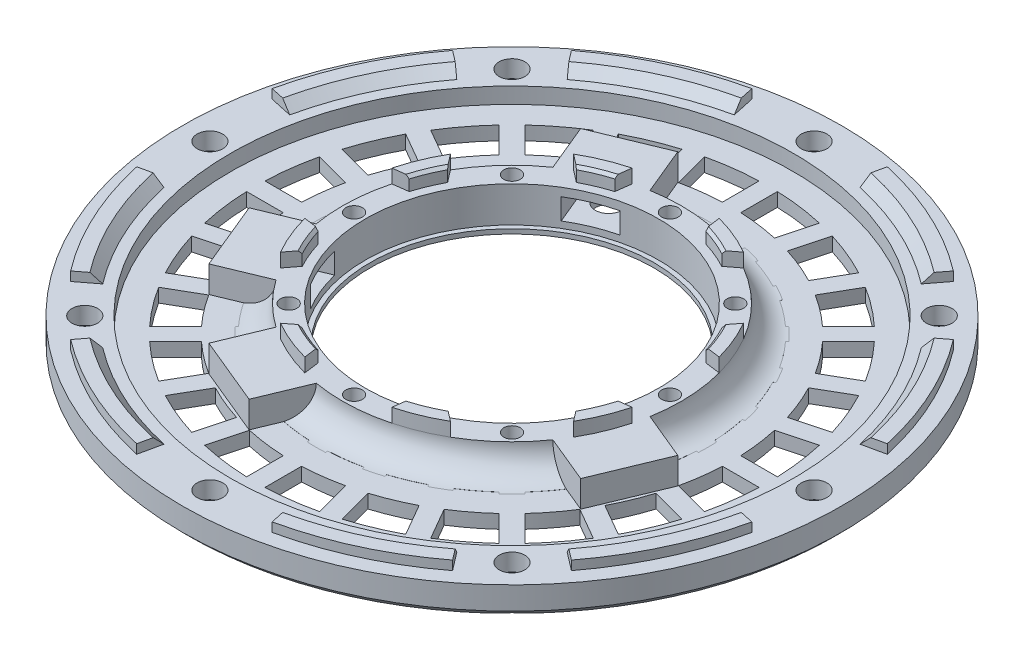
SolidWorks part; units mm, degrees
ref_plane "Front Plane" through (0, 0, 0) normal (0, 0, 1) x (1, 0, 0)
ref_plane "Top Plane" through (0, 0, 0) normal (0, 1, 0) x (1, 0, 0)
ref_plane "Right Plane" through (0, 0, 0) normal (1, 0, 0) x (0, 0, -1)
sketch "Sketch1" plane through (0, 0, 0) normal (0, 1, 0) x (1, 0, 0)
  circle A0 centre (0, 0) radius 16.025
  circle A1 centre (0, 0) radius 36
  dimension "D1" = 32.05
  dimension "D2" = 72
extrude "Boss-Extrude1" add sketch "Sketch1" along normal blind 1
sketch "Sketch2" plane through (0, 0, 0) normal (0, -1, 0) x (1, 0, 0)
  circle A0 centre (0, 0) radius 17.25 construction
  circle A1 centre (0, 0) radius 18.5 construction
  circle A2 centre (0, 0) radius 18.5
  circle A3 centre (0, 0) radius 16.025 construction
  circle A4 centre (0, 0) radius 16.025
  arc A5 (-1.2, 18.461) -> (-4.705, 17.8917) centre (0, 0) ccw construction
  point P3 (0, -17.25)
extrude "Boss-Extrude2" add sketch "Sketch2" against normal offset from surface (3.9 mm away) 3.9 up to face at (0, 0, 36)
fillet "Fillet1" radius 2.9 1 edges at (0, 1, 18.5)
sketch "Sketch4" plane through (0, 0, 0) normal (0, 1, 0) x (1, 0, 0)
  circle A0 centre (0, 0) radius 15.525
  circle A1 centre (0, 0) radius 36
  circle A2 centre (0, 0) radius 36
  circle A3 centre (0, 0) radius 16.025 construction
  dimension "D2" = 0.5
  dimension "D1" = 0
extrude "Boss-Extrude3" add sketch "Sketch4" against normal blind 0.5
sketch "Sketch5" plane through (0, 1, 0) normal (0, 1, 0) x (1, 0, 0)
  line L0 (27.99, -0.75) -> (19.9859, -0.75) construction
  line L1 (19.9859, 0.75) -> (27.99, 0.75) construction
  line L2 (27.99, -0.75) -> (19.9859, -0.75) construction
  line L3 (19.9859, 0.75) -> (27.99, 0.75) construction
  line L4 (0, 0) -> (36, 0) construction
  line L5 (0, 0) -> (34.7733, 9.3175) construction
  line L6 (34.7733, 9.3175) -> (36, 0) construction
  line L7 (0, 0) -> (35.3867, 4.6587) construction
  line L8 (27.99, 1) -> (21.1263, 1)
  line L9 (27.295, 6.2784) -> (20.6653, 4.502)
  line L10 (27.99, -1) -> (21.1263, -1)
  line L11 (27.295, -6.2784) -> (20.6653, -4.502)
  line L12 (26.7774, -8.2103) -> (20.1477, -6.4338)
  line L13 (24.74, -13.129) -> (18.796, -9.6971)
  line L14 (23.74, -14.861) -> (17.796, -11.4292)
  line L15 (20.499, -19.0848) -> (15.6457, -14.2315)
  line L16 (19.0848, -20.499) -> (14.2315, -15.6457)
  line L17 (14.861, -23.74) -> (11.4292, -17.796)
  line L18 (13.129, -24.74) -> (9.6971, -18.796)
  line L19 (8.2103, -26.7774) -> (6.4338, -20.1477)
  line L20 (6.2784, -27.295) -> (4.502, -20.6653)
  line L21 (1, -27.99) -> (1, -21.1263)
  line L22 (-1, -27.99) -> (-1, -21.1263)
  line L23 (-6.2784, -27.295) -> (-4.502, -20.6653)
  line L24 (-8.2103, -26.7774) -> (-6.4338, -20.1477)
  line L25 (-13.129, -24.74) -> (-9.6971, -18.796)
  line L26 (-14.861, -23.74) -> (-11.4292, -17.796)
  line L27 (-19.0848, -20.499) -> (-14.2315, -15.6457)
  line L28 (-20.499, -19.0848) -> (-15.6457, -14.2315)
  line L29 (-23.74, -14.861) -> (-17.796, -11.4292)
  line L30 (-24.74, -13.129) -> (-18.796, -9.6971)
  line L31 (-26.7774, -8.2103) -> (-20.1477, -6.4338)
  line L32 (-27.295, -6.2784) -> (-20.6653, -4.502)
  line L33 (-27.99, -1) -> (-21.1263, -1)
  line L34 (-27.99, 1) -> (-21.1263, 1)
  line L35 (-27.295, 6.2784) -> (-20.6653, 4.502)
  line L36 (-26.7774, 8.2103) -> (-20.1477, 6.4338)
  line L37 (-24.74, 13.129) -> (-18.796, 9.6971)
  line L38 (-23.74, 14.861) -> (-17.796, 11.4292)
  line L39 (-20.499, 19.0848) -> (-15.6457, 14.2315)
  line L40 (-19.0848, 20.499) -> (-14.2315, 15.6457)
  line L41 (-14.861, 23.74) -> (-11.4292, 17.796)
  line L42 (-13.129, 24.74) -> (-9.6971, 18.796)
  line L43 (-8.2103, 26.7774) -> (-6.4338, 20.1477)
  line L44 (-6.2784, 27.295) -> (-4.502, 20.6653)
  line L45 (-1, 27.99) -> (-1, 21.1263)
  line L46 (1, 27.99) -> (1, 21.1263)
  line L47 (6.2784, 27.295) -> (4.502, 20.6653)
  line L48 (8.2103, 26.7774) -> (6.4338, 20.1477)
  line L49 (13.129, 24.74) -> (9.6971, 18.796)
  line L50 (14.861, 23.74) -> (11.4292, 17.796)
  line L51 (19.0848, 20.499) -> (14.2315, 15.6457)
  line L52 (20.499, 19.0848) -> (15.6457, 14.2315)
  line L53 (23.74, 14.861) -> (17.796, 11.4292)
  line L54 (24.74, 13.129) -> (18.796, 9.6971)
  line L55 (26.7774, 8.2103) -> (20.1477, 6.4338)
  line L56 (0, 0) -> (21.1263, 1) construction
  circle A0 centre (0, 0) radius 21.15 construction
  circle A2 centre (0, 0) radius 36 construction
  arc A3 (21.1263, 1) -> (20.6653, 4.502) centre (0, 0) ccw
  arc A4 (27.99, 1) -> (27.295, 6.2784) centre (0, 0) ccw
  arc A5 (27.295, -6.2784) -> (27.99, -1) centre (0, 0) ccw
  arc A6 (20.6653, -4.502) -> (21.1263, -1) centre (0, 0) ccw
  arc A7 (24.74, -13.129) -> (26.7774, -8.2103) centre (0, 0) ccw
  arc A8 (18.796, -9.6971) -> (20.1477, -6.4338) centre (0, 0) ccw
  arc A9 (20.499, -19.0848) -> (23.74, -14.861) centre (0, 0) ccw
  arc A10 (15.6457, -14.2315) -> (17.796, -11.4292) centre (0, 0) ccw
  arc A11 (14.861, -23.74) -> (19.0848, -20.499) centre (0, 0) ccw
  arc A12 (11.4292, -17.796) -> (14.2315, -15.6457) centre (0, 0) ccw
  arc A13 (8.2103, -26.7774) -> (13.129, -24.74) centre (0, 0) ccw
  arc A14 (6.4338, -20.1477) -> (9.6971, -18.796) centre (0, 0) ccw
  arc A15 (1, -27.99) -> (6.2784, -27.295) centre (0, 0) ccw
  arc A16 (1, -21.1263) -> (4.502, -20.6653) centre (0, 0) ccw
  arc A17 (-6.2784, -27.295) -> (-1, -27.99) centre (0, 0) ccw
  arc A18 (-4.502, -20.6653) -> (-1, -21.1263) centre (0, 0) ccw
  arc A19 (-13.129, -24.74) -> (-8.2103, -26.7774) centre (0, 0) ccw
  arc A20 (-9.6971, -18.796) -> (-6.4338, -20.1477) centre (0, 0) ccw
  arc A21 (-19.0848, -20.499) -> (-14.861, -23.74) centre (0, 0) ccw
  arc A22 (-14.2315, -15.6457) -> (-11.4292, -17.796) centre (0, 0) ccw
  arc A23 (-23.74, -14.861) -> (-20.499, -19.0848) centre (0, 0) ccw
  arc A24 (-17.796, -11.4292) -> (-15.6457, -14.2315) centre (0, 0) ccw
  arc A25 (-26.7774, -8.2103) -> (-24.74, -13.129) centre (0, 0) ccw
  arc A26 (-20.1477, -6.4338) -> (-18.796, -9.6971) centre (0, 0) ccw
  arc A27 (-27.99, -1) -> (-27.295, -6.2784) centre (0, 0) ccw
  arc A28 (-21.1263, -1) -> (-20.6653, -4.502) centre (0, 0) ccw
  arc A29 (-27.295, 6.2784) -> (-27.99, 1) centre (0, 0) ccw
  arc A30 (-20.6653, 4.502) -> (-21.1263, 1) centre (0, 0) ccw
  arc A31 (-24.74, 13.129) -> (-26.7774, 8.2103) centre (0, 0) ccw
  arc A32 (-18.796, 9.6971) -> (-20.1477, 6.4338) centre (0, 0) ccw
  arc A33 (-20.499, 19.0848) -> (-23.74, 14.861) centre (0, 0) ccw
  arc A34 (-15.6457, 14.2315) -> (-17.796, 11.4292) centre (0, 0) ccw
  arc A35 (-14.861, 23.74) -> (-19.0848, 20.499) centre (0, 0) ccw
  arc A36 (-11.4292, 17.796) -> (-14.2315, 15.6457) centre (0, 0) ccw
  arc A37 (-8.2103, 26.7774) -> (-13.129, 24.74) centre (0, 0) ccw
  arc A38 (-6.4338, 20.1477) -> (-9.6971, 18.796) centre (0, 0) ccw
  arc A39 (-1, 27.99) -> (-6.2784, 27.295) centre (0, 0) ccw
  arc A40 (-1, 21.1263) -> (-4.502, 20.6653) centre (0, 0) ccw
  arc A41 (6.2784, 27.295) -> (1, 27.99) centre (0, 0) ccw
  arc A42 (4.502, 20.6653) -> (1, 21.1263) centre (0, 0) ccw
  arc A43 (13.129, 24.74) -> (8.2103, 26.7774) centre (0, 0) ccw
  arc A44 (9.6971, 18.796) -> (6.4338, 20.1477) centre (0, 0) ccw
  arc A45 (19.0848, 20.499) -> (14.861, 23.74) centre (0, 0) ccw
  arc A46 (14.2315, 15.6457) -> (11.4292, 17.796) centre (0, 0) ccw
  arc A47 (23.74, 14.861) -> (20.499, 19.0848) centre (0, 0) ccw
  arc A48 (17.796, 11.4292) -> (15.6457, 14.2315) centre (0, 0) ccw
  arc A49 (26.7774, 8.2103) -> (24.74, 13.129) centre (0, 0) ccw
  arc A50 (20.1477, 6.4338) -> (18.796, 9.6971) centre (0, 0) ccw
  dimension "D1" = 15
  dimension "D2" = 1
  dimension "D4" = 21.15
  dimension "D3" = 24
extrude "Cut-Extrude1" cut sketch "Sketch5" against normal through all both and the other way through all
sketch "Sketch22" plane through (0, -0.5, 0) normal (0, -1, 0) x (1, 0, 0)
  circle A0 centre (0, 0) radius 21.15
  circle A1 centre (0, 0) radius 24.0078
  arc A2 (-14.861, 23.74) -> (-19.0848, 20.499) centre (0, 0) ccw construction
  dimension "D1" = 4
extrude "Boss-Extrude10" add sketch "Sketch22" against normal up to surface (1.5 mm away) up to face at (0, 1, 0)
sketch "Sketch7" plane through (0, 3.9, 0) normal (0, 1, 0) x (1, 0, 0)
  line L0 (0, 0) -> (0, 17.25) construction
  circle A0 centre (0, 17.25) radius 0.9
  circle A1 centre (12.1976, 12.1976) radius 0.9
  circle A2 centre (17.25, 0) radius 0.9
  circle A3 centre (12.1976, -12.1976) radius 0.9
  circle A4 centre (0, -17.25) radius 0.9
  circle A5 centre (-12.1976, -12.1976) radius 0.9
  circle A6 centre (-17.25, 0) radius 0.9
  circle A7 centre (-12.1976, 12.1976) radius 0.9
  point P21 (0, 0)
  dimension "D1" = 1.8
  dimension "D2" = 8
extrude "Cut-Extrude2" cut sketch "Sketch7" against normal through all
sketch "Sketch8" plane through (0, 1, 0) normal (0, 1, 0) x (1, 0, 0)
  arc A0 (-30.7407, -0.7544) -> (-30.0499, -6.5245) centre (0, 0) ccw construction
  arc A1 (-30.7407, -0.7544) -> (-30.0499, -6.5245) centre (0, 0) ccw construction
  arc A2 (-30.0499, 6.5245) -> (-30.7407, 0.7544) centre (0, 0) ccw construction
  arc A3 (-30.0499, 6.5245) -> (-30.7407, 0.7544) centre (0, 0) ccw construction
  circle A5 centre (0, 0) radius 30.75
  circle A6 centre (0, 0) radius 36 construction
  circle A7 centre (0, 0) radius 36
extrude "Boss-Extrude4" add sketch "Sketch8" along normal blind 1.7378
sketch "Sketch9" plane through (0, 2.7378, 0) normal (0, 1, 0) x (1, 0, 0)
  line L0 (0, 0) -> (-30.0499, 6.5245) construction
  line L1 (0, 0) -> (-30.0499, -6.5245) construction
  line L2 (-30.0499, 6.5245) -> (-30.0499, -6.5245) construction
  line L3 (-27.3707, 21.0023) -> (-23.9989, 18.415) construction
  line L4 (0, 0) -> (0, 36) construction
  line L5 (0, 0) -> (-25.4558, 25.4558) construction
  line L6 (-24.3956, 18.7194) -> (0, 0) construction
  line L7 (-24.3956, 18.7194) -> (-28.5607, 21.9154) construction
  line L8 (-30.0499, 6.5245) -> (-35.1803, 7.6384) construction
  line L9 (-27.3521, 20.862) -> (-25.3687, 19.3401)
  line L10 (-31.2086, 14.47) -> (0, 0) construction
  line L11 (-33.5954, 7.3966) -> (-31.1523, 6.8662)
  line L12 (-7.3966, 33.5954) -> (-6.8662, 31.1523)
  line L13 (-20.862, 27.3521) -> (-19.3401, 25.3687)
  arc A0 (-30.0499, 6.5245) -> (-24.3956, 18.7194) centre (0, 0) cw construction
  arc A1 (-35.1803, 7.6384) -> (-28.5607, 21.9154) centre (0, 0) cw construction
  circle A2 centre (0, 0) radius 36 construction
  circle A3 centre (0, 0) radius 30.75 construction
  arc A4 (-27.2914, 20.9414) -> (-33.6168, 7.2989) centre (0, 0) ccw construction
  arc A5 (-31.1523, 6.8662) -> (-25.3687, 19.3401) centre (0, 0) cw
  arc A6 (-33.5954, 7.3966) -> (-27.3521, 20.862) centre (0, 0) cw
  circle A7 centre (0, 0) radius 36 construction
  arc A8 (-6.8662, 31.1523) -> (-19.3401, 25.3687) centre (0, 0) ccw
  arc A9 (-7.3966, 33.5954) -> (-20.862, 27.3521) centre (0, 0) ccw
  dimension "D2" = 0.1
  dimension "D3" = 45
  dimension "D4" = 0.1
  dimension "D1" = 2.5
extrude "Boss-Extrude5" add sketch "Sketch9" along normal blind 1
ref_axis "Axis1" through (0, -0.795, 0) along (0, 1, 0)
pattern_circular "CirPattern1" count 4 over 360 about axis through (0, -0.795, 0) along (0, 1, 0) of "Boss-Extrude5"
chamfer "Chamfer1" distance 1 angle 45 8 edges at (-28.9406, 3.7378, -13.4184) (-13.4184, 3.7378, -28.9406) (13.4184, 3.7378, -28.9406) (28.9406, 3.7378, -13.4184) (28.9406, 3.7378, 13.4184) (13.4184, 3.7378, 28.9406) (-13.4184, 3.7378, 28.9406) (-28.9406, 3.7378, 13.4184)
sketch "Sketch10" plane through (0, 2.7378, 0) normal (0, 1, 0) x (1, 0, 0)
  line L0 (0, 0) -> (0, 36) construction
  circle A0 centre (0, 0) radius 36 construction
  circle A1 centre (0, 33) radius 1.4 construction
  circle A2 centre (0, 33) radius 1.4
  circle A3 centre (23.3345, 23.3345) radius 1.4
  circle A4 centre (33, 0) radius 1.4
  circle A5 centre (23.3345, -23.3345) radius 1.4
  circle A6 centre (0, -33) radius 1.4
  circle A7 centre (-23.3345, -23.3345) radius 1.4
  circle A8 centre (-33, 0) radius 1.4
  circle A9 centre (-23.3345, 23.3345) radius 1.4
  point P26 (0, 0)
  dimension "D1" = 8
extrude "Cut-Extrude3" cut sketch "Sketch10" against normal through all both and the other way through all
chamfer "Chamfer2" distance 0.75 angle 45 1 edges at (0, -0.5, 36)
hole_wizard "CSK for M2.5 Flat Head Machine Screw1" positions "Sketch11" profile "Sketch12" countersink size "M2.5" standard "ANSI Metric" end condition through all
sketch "Sketch11" plane through (0, -0.5, 0) normal (0, -1, 0) x (-1, 0, 0)
  point P0 (0, -33)
  point P3 (23.3345, -23.3345)
  point P6 (33, 0)
  point P9 (23.3345, 23.3345)
  point P12 (0, 33)
  point P15 (-23.3345, 23.3345)
  point P18 (-33, 0)
  point P21 (-23.3345, -23.3345)
sketch "Sketch12" plane through (0, -0.5, 33) normal (1, 0, 0) x (0, 0, -1)
  line L0 (0, 0) -> (0, 4.4)
  line L1 (0, 4.4) -> (1.35, 4.4)
  line L2 (1.35, 4.4) -> (1.35, 1.4)
  line L3 (1.35, 1.4) -> (2.75, 0)
  line L5 (2.75, 0) -> (0, 0)
  line L6 (-1.35, 1.4) -> (-2.75, 0) construction
  line L11 (0, -6.35) -> (0, 107.95) construction
  dimension "Thru Hole Dia." = 2.7
  dimension "Thru Hole Depth" = 4.4
  dimension "Near C'Sink Dia." = 5.5
  dimension "Near C'Sink Angle" = 90
sketch "Sketch13" plane through (0, 3.9, 0) normal (0, 1, 0) x (1, 0, 0)
  line L0 (0, 0) -> (-7.0796, 17.0918) construction
  line L1 (0, 0) -> (0, 18.5) construction
  line L2 (-9.2808, 16.0037) -> (-7.9403, 14.9751)
  line L3 (-4.7538, 17.8788) -> (-4.9743, 16.2037)
  line L4 (4.7538, 17.8788) -> (4.9743, 16.2037)
  line L5 (9.2808, 16.0037) -> (7.9403, 14.9751)
  line L6 (16.0037, 9.2808) -> (14.9751, 7.9403)
  line L7 (17.8788, 4.7538) -> (16.2037, 4.9743)
  line L8 (17.8788, -4.7538) -> (16.2037, -4.9743)
  line L9 (16.0037, -9.2808) -> (14.9751, -7.9403)
  line L10 (9.2808, -16.0037) -> (7.9403, -14.9751)
  line L11 (4.7538, -17.8788) -> (4.9743, -16.2037)
  line L12 (-4.7538, -17.8788) -> (-4.9743, -16.2037)
  line L13 (-9.2808, -16.0037) -> (-7.9403, -14.9751)
  line L14 (-16.0037, -9.2808) -> (-14.9751, -7.9403)
  line L15 (-17.8788, -4.7538) -> (-16.2037, -4.9743)
  line L16 (-17.8788, 4.7538) -> (-16.2037, 4.9743)
  line L17 (-16.0037, 9.2808) -> (-14.9751, 7.9403)
  circle A0 centre (0, 0) radius 18.5 construction
  arc A1 (-7.9403, 14.9751) -> (-4.9743, 16.2037) centre (0, 0) cw
  arc A2 (-9.2808, 16.0037) -> (-4.7538, 17.8788) centre (0, 0) cw
  arc A3 (4.9743, 16.2037) -> (7.9403, 14.9751) centre (0, 0) cw
  arc A4 (4.7538, 17.8788) -> (9.2808, 16.0037) centre (0, 0) cw
  arc A5 (14.9751, 7.9403) -> (16.2037, 4.9743) centre (0, 0) cw
  arc A6 (16.0037, 9.2808) -> (17.8788, 4.7538) centre (0, 0) cw
  arc A7 (16.2037, -4.9743) -> (14.9751, -7.9403) centre (0, 0) cw
  arc A8 (17.8788, -4.7538) -> (16.0037, -9.2808) centre (0, 0) cw
  arc A9 (7.9403, -14.9751) -> (4.9743, -16.2037) centre (0, 0) cw
  arc A10 (9.2808, -16.0037) -> (4.7538, -17.8788) centre (0, 0) cw
  arc A11 (-4.9743, -16.2037) -> (-7.9403, -14.9751) centre (0, 0) cw
  arc A12 (-4.7538, -17.8788) -> (-9.2808, -16.0037) centre (0, 0) cw
  arc A13 (-14.9751, -7.9403) -> (-16.2037, -4.9743) centre (0, 0) cw
  arc A14 (-16.0037, -9.2808) -> (-17.8788, -4.7538) centre (0, 0) cw
  arc A15 (-16.2037, 4.9743) -> (-14.9751, 7.9403) centre (0, 0) cw
  arc A16 (-17.8788, 4.7538) -> (-16.0037, 9.2808) centre (0, 0) cw
  point P12 (-6.4865, 15.6598)
  point P20 (6.4865, 15.6598)
  point P25 (15.6598, 6.4865)
  point P30 (15.6598, -6.4865)
  point P35 (6.4865, -15.6598)
  point P40 (-6.4865, -15.6598)
  point P45 (-15.6598, -6.4865)
  point P50 (-15.6598, 6.4865)
  point P51 (0, 0)
  dimension "D1" = 22.5
  dimension "D2" = 30
  dimension "D3" = 1.55
  dimension "D4" = 4.9
  dimension "D5" = 8
extrude "Boss-Extrude6" add sketch "Sketch13" along normal blind 1.5
chamfer "Chamfer3" distance 0.3 angle 45 8 edges at (-15.6598, 5.4, -6.4865) (-15.6598, 5.4, 6.4865) (-6.4865, 5.4, 15.6598) (6.4865, 5.4, 15.6598) (15.6598, 5.4, 6.4865) (15.6598, 5.4, -6.4865) (6.4865, 5.4, -15.6598) (-6.4865, 5.4, -15.6598)
sketch "Sketch14" plane through (0, -0.5, 0) normal (0, -1, 0) x (1, 0, 0)
  line L0 (0, 0) -> (25.4558, -25.4558) construction
  line L1 (0, 0) -> (0, -36) construction
  line L6 (0, 0) -> (-19.9789, 8.2755) construction
  line L7 (0, 0) -> (-8.2755, -19.9789) construction
  circle A0 centre (0, 0) radius 36 construction
  circle A1 centre (0, 0) radius 16.025 construction
  circle A6 centre (-18.0157, 7.4623) radius 1.45
  circle A7 centre (-18.0157, 7.4623) radius 2.125 construction
  circle A9 centre (-7.4623, -18.0157) radius 1.45
  circle A10 centre (-7.4623, -18.0157) radius 2.125 construction
  circle A11 centre (18.0157, 7.4623) radius 1.45
  circle A12 centre (-7.4623, 18.0157) radius 1.45
  point P25 (-14.8052, 6.1325)
  point P28 (-16.676, 6.9074)
  dimension "D2" = 2.9
  dimension "D3" = 3.475
  dimension "D5" = 4.25
  dimension "D7" = 21.625
  dimension "D1" = 45
  dimension "D4" = 112.5
  dimension "D6" = 22.5
sketch "Sketch15" plane through (0, 1, 0) normal (0, 1, 0) x (1, 0, 0)
  line L0 (-9.8825, 13.2519) -> (-12.8051, 20.3077)
  line L1 (-9.8825, 13.2519) -> (-2.3825, 16.3585)
  line L2 (-12.8051, 20.3077) -> (-5.3051, 23.4143)
  line L3 (-2.3825, 16.3585) -> (-5.3051, 23.4143)
  line L4 (-9.8825, 13.2519) -> (-5.3051, 23.4143) construction
  line L5 (-12.8051, 20.3077) -> (-2.3825, 16.3585) construction
  line L6 (0, 0) -> (-8.2755, 19.9789) construction
  line L7 (2.3825, 16.3585) -> (5.3051, 23.4143) [skipped]
  line L8 (2.3825, 16.3585) -> (9.8825, 13.2519) [skipped]
  line L9 (5.3051, 23.4143) -> (12.8051, 20.3077) [skipped]
  line L10 (9.8825, 13.2519) -> (12.8051, 20.3077) [skipped]
  line L11 (2.3825, 16.3585) -> (12.8051, 20.3077) construction
  line L12 (5.3051, 23.4143) -> (9.8825, 13.2519) construction
  line L13 (13.2519, 9.8825) -> (20.3077, 12.8051) [skipped]
  line L14 (13.2519, 9.8825) -> (16.3585, 2.3825) [skipped]
  line L15 (20.3077, 12.8051) -> (23.4143, 5.3051) [skipped]
  line L16 (16.3585, 2.3825) -> (23.4143, 5.3051) [skipped]
  line L17 (13.2519, 9.8825) -> (23.4143, 5.3051) construction
  line L18 (20.3077, 12.8051) -> (16.3585, 2.3825) construction
  line L19 (16.3585, -2.3825) -> (23.4143, -5.3051)
  line L20 (16.3585, -2.3825) -> (13.2519, -9.8825)
  line L21 (23.4143, -5.3051) -> (20.3077, -12.8051)
  line L22 (13.2519, -9.8825) -> (20.3077, -12.8051)
  line L23 (16.3585, -2.3825) -> (20.3077, -12.8051) construction
  line L24 (23.4143, -5.3051) -> (13.2519, -9.8825) construction
  line L25 (9.8825, -13.2519) -> (12.8051, -20.3077) [skipped]
  line L26 (9.8825, -13.2519) -> (2.3825, -16.3585) [skipped]
  line L27 (12.8051, -20.3077) -> (5.3051, -23.4143) [skipped]
  line L28 (2.3825, -16.3585) -> (5.3051, -23.4143) [skipped]
  line L29 (9.8825, -13.2519) -> (5.3051, -23.4143) construction
  line L30 (12.8051, -20.3077) -> (2.3825, -16.3585) construction
  line L31 (-2.3825, -16.3585) -> (-5.3051, -23.4143)
  line L32 (-2.3825, -16.3585) -> (-9.8825, -13.2519)
  line L33 (-5.3051, -23.4143) -> (-12.8051, -20.3077)
  line L34 (-9.8825, -13.2519) -> (-12.8051, -20.3077)
  line L35 (-2.3825, -16.3585) -> (-12.8051, -20.3077) construction
  line L36 (-5.3051, -23.4143) -> (-9.8825, -13.2519) construction
  line L37 (-13.2519, -9.8825) -> (-20.3077, -12.8051)
  line L38 (-13.2519, -9.8825) -> (-16.3585, -2.3825)
  line L39 (-20.3077, -12.8051) -> (-23.4143, -5.3051)
  line L40 (-16.3585, -2.3825) -> (-23.4143, -5.3051)
  line L41 (-13.2519, -9.8825) -> (-23.4143, -5.3051) construction
  line L42 (-20.3077, -12.8051) -> (-16.3585, -2.3825) construction
  line L43 (-16.3585, 2.3825) -> (-23.4143, 5.3051) [skipped]
  line L44 (-16.3585, 2.3825) -> (-13.2519, 9.8825) [skipped]
  line L45 (-23.4143, 5.3051) -> (-20.3077, 12.8051) [skipped]
  line L46 (-13.2519, 9.8825) -> (-20.3077, 12.8051) [skipped]
  line L47 (-16.3585, 2.3825) -> (-20.3077, 12.8051) construction
  line L48 (-23.4143, 5.3051) -> (-13.2519, 9.8825) construction
  line L49 (0, 0) -> (-10.7181, 25.8758) construction
  arc A0 (-12.8595, 20.2733) -> (-16.2542, 17.6685) centre (0, 0) ccw construction
  arc A1 (-8.2103, 26.7774) -> (-13.129, 24.74) centre (0, 0) ccw construction
  circle A2 centre (0, 0) radius 16.025 construction
  point P1 (-7.5938, 18.3331)
  point P9 (7.5938, 18.3331)
  point P18 (18.3331, 7.5938)
  point P23 (18.3331, -7.5938)
  point P28 (7.5938, -18.3331)
  point P33 (-7.5938, -18.3331)
  point P38 (-18.3331, -7.5938)
  point P43 (-18.3331, 7.5938)
  point P48 (0, 0)
  dimension "D1" = 7.5
  dimension "D2" = 8
extrude "Boss-Extrude7" add sketch "Sketch15" along normal up to surface (2.9 mm away) up to face at (0, 3.9, -16.35)
extrude "Cut-Extrude4" cut sketch "Sketch14" against normal blind 3.5
sketch "Sketch16" [suppressed] plane through (0, -0.5, 0) normal (0, -1, 0) x (1, 0, 0)
  line L0 (0, 0) -> (23.3345, -23.3345) construction
  line L1 (9.9327, 7.9941) -> (22.7049, -7.8756) construction
  line L2 (0, 0) -> (0, -17.25) construction
  line L3 (0, 0) -> (9.9327, 7.9941) construction
  line L4 (19.041, 8.4876) -> (13.7643, 13.7643) construction
  line L5 (0, 0) -> (13.7643, 13.7643) construction
  line L6 (25.4316, -5.6811) -> (27.9064, -3.2063) construction
  line L7 (27.9064, -3.2063) -> (12.3501, 12.3501) construction
  circle A0 centre (0, 0) radius 12.75 construction
  circle A1 centre (25.4316, -5.6811) radius 1.65
  circle A2 centre (25.4316, -5.6811) radius 3.5 construction
  circle A3 centre (18.0157, 7.4623) radius 1.45 construction
  circle A4 centre (5.6811, -25.4316) radius 1.65
  dimension "D1" = 25.5
  dimension "D2" = 3.3
  dimension "D3" = 7
  dimension "D4" = 2
  dimension "D5" = 22
sketch "Sketch17" [suppressed] plane through (0, -0.5, 0) normal (0, -1, 0) x (1, 0, 0)
  line L0 (24.74, -13.129) -> (18.796, -9.6971) construction
  line L1 (24.74, -13.129) -> (18.796, -9.6971)
  line L2 (0, 0) -> (12.1976, -12.1976) construction
  line L3 (13.129, -24.74) -> (9.6971, -18.796)
  arc A0 (18.796, -9.6971) -> (20.1477, -6.4338) centre (0, 0) ccw construction
  arc A1 (24.74, -13.129) -> (26.7774, -8.2103) centre (0, 0) ccw construction
  arc A4 (18.796, -9.6971) -> (19.6572, -7.8049) centre (0, 0) ccw
  arc A5 (24.74, -13.129) -> (25.4284, -11.7403) centre (0, 0) ccw
  arc A8 (25.4284, -11.7403) -> (19.6572, -7.8049) centre (25.1212, -5.9915) ccw
  arc A9 (11.7403, -25.4284) -> (7.8049, -19.6572) centre (5.9915, -25.1212) cw
  arc A10 (13.129, -24.74) -> (11.7403, -25.4284) centre (0, 0) cw
  arc A11 (9.6971, -18.796) -> (7.8049, -19.6572) centre (0, 0) cw
extrude "Boss-Extrude8" [suppressed] add sketch "Sketch17" against normal up to surface (1.5 mm away)
sketch "Sketch18" [suppressed] plane through (0, 1, 0) normal (0, 1, 0) x (1, 0, 0)
  line L0 (0, 0) -> (25.4316, 5.6811) construction
  line L1 (24.5595, 9.5849) -> (28.8833, 10.5508)
  line L2 (26.3036, 1.7774) -> (30.6274, 2.7432)
  line L3 (0, 0) -> (23.3345, 23.3345) construction
  line L4 (9.5849, 24.5595) -> (10.5508, 28.8833)
  line L5 (1.7774, 26.3036) -> (2.7432, 30.6274)
  arc A0 (24.5595, 9.5849) -> (26.3036, 1.7774) centre (25.4316, 5.6811) ccw
  circle A1 centre (0, 0) radius 30.75 construction
  circle A2 centre (0, 0) radius 30.75 construction
  arc A3 (30.6274, 2.7432) -> (28.8833, 10.5508) centre (0, 0) ccw
  arc A4 (2.7432, 30.6274) -> (10.5508, 28.8833) centre (0, 0) cw
  arc A5 (9.5849, 24.5595) -> (1.7774, 26.3036) centre (5.6811, 25.4316) cw
  circle A6 centre (23.3345, 23.3345) radius 1.4 construction
  dimension "D1" = 8
extrude "Boss-Extrude9" [suppressed] add sketch "Sketch18" along normal up to surface (1.7378 mm away)
extrude "Cut-Extrude5" [suppressed] cut sketch "Sketch16" against normal through all
sketch "Sketch19" [suppressed] plane through (0, 2.7378, 0) normal (0, 1, 0) x (1, 0, 0)
  line L0 (0, 0) -> (25.1212, 5.9915) construction
  line L1 (28.1539, 6.7147) -> (26.0112, 8.9794)
  line L2 (26.0112, 8.9794) -> (22.9785, 8.2561)
  line L3 (22.9785, 8.2561) -> (22.0886, 5.2682)
  line L4 (22.0886, 5.2682) -> (24.2313, 3.0035)
  line L5 (24.2313, 3.0035) -> (27.2639, 3.7268)
  line L6 (27.2639, 3.7268) -> (28.1539, 6.7147)
  line L7 (0, 0) -> (23.3345, 23.3345) construction
  line L8 (3.7268, 27.2639) -> (6.7147, 28.1539)
  line L9 (3.0035, 24.2313) -> (3.7268, 27.2639)
  line L10 (5.2682, 22.0886) -> (3.0035, 24.2313)
  line L11 (8.2561, 22.9785) -> (5.2682, 22.0886)
  line L12 (8.9794, 26.0112) -> (8.2561, 22.9785)
  line L13 (6.7147, 28.1539) -> (8.9794, 26.0112)
  circle A0 centre (25.1212, 5.9915) radius 2.7 construction
  circle A1 centre (23.3345, 23.3345) radius 1.35 construction
  dimension "D1" = 5.4
extrude "Cut-Extrude6" [suppressed] cut sketch "Sketch19" against normal blind 2.4
sketch "Sketch20" plane through (0, 3, 0) normal (0, -1, 0) x (1, 0, 0)
  line L0 (0, 0) -> (-18.0157, 7.4623) construction
  line L5 (-15.7712, 9.1845) -> (-13.6935, 8.3239)
  line L6 (-15.402, 6.3797) -> (-15.7712, 9.1845) construction
  line L16 (-15.7712, 9.1845) -> (-18.3849, 10.2671)
  line L17 (-18.3849, 10.2671) -> (-20.6293, 8.5449)
  line L18 (-20.6293, 8.5449) -> (-20.2601, 5.7401)
  line L19 (-20.2601, 5.7401) -> (-17.6464, 4.6575)
  line L20 (-17.6464, 4.6575) -> (-15.402, 6.3797) construction
  line L21 (-13.6935, 8.3239) -> (-15.5687, 3.7969)
  line L28 (-15.5687, 3.7969) -> (-17.6464, 4.6575)
  line L29 (-8.3239, 13.6935) -> (-9.1845, 15.7712)
  line L30 (-10.2671, 18.3849) -> (-9.1845, 15.7712)
  line L31 (-8.5449, 20.6293) -> (-10.2671, 18.3849)
  line L32 (-5.7401, 20.2601) -> (-8.5449, 20.6293)
  line L33 (-4.6575, 17.6464) -> (-5.7401, 20.2601)
  line L34 (-4.6575, 17.6464) -> (-3.7969, 15.5687)
  line L35 (-3.7969, 15.5687) -> (-8.3239, 13.6935)
  line L36 (3.7969, 15.5687) -> (4.6575, 17.6464) [skipped]
  line L37 (5.7401, 20.2601) -> (4.6575, 17.6464) [skipped]
  line L38 (8.5449, 20.6293) -> (5.7401, 20.2601) [skipped]
  line L39 (10.2671, 18.3849) -> (8.5449, 20.6293) [skipped]
  line L46 (9.1845, 15.7712) -> (10.2671, 18.3849) [skipped]
  line L47 (9.1845, 15.7712) -> (8.3239, 13.6935) [skipped]
  line L48 (8.3239, 13.6935) -> (3.7969, 15.5687) [skipped]
  line L49 (13.6935, 8.3239) -> (15.7712, 9.1845)
  line L50 (18.3849, 10.2671) -> (15.7712, 9.1845)
  line L51 (20.6293, 8.5449) -> (18.3849, 10.2671)
  line L52 (20.2601, 5.7401) -> (20.6293, 8.5449)
  line L53 (17.6464, 4.6575) -> (20.2601, 5.7401)
  line L54 (17.6464, 4.6575) -> (15.5687, 3.7969)
  line L55 (15.5687, 3.7969) -> (13.6935, 8.3239)
  line L56 (15.5687, -3.7969) -> (17.6464, -4.6575) [skipped]
  line L57 (20.2601, -5.7401) -> (17.6464, -4.6575) [skipped]
  line L58 (20.6293, -8.5449) -> (20.2601, -5.7401) [skipped]
  line L59 (18.3849, -10.2671) -> (20.6293, -8.5449) [skipped]
  line L60 (15.7712, -9.1845) -> (18.3849, -10.2671) [skipped]
  line L61 (15.7712, -9.1845) -> (13.6935, -8.3239) [skipped]
  line L62 (13.6935, -8.3239) -> (15.5687, -3.7969) [skipped]
  line L63 (8.3239, -13.6935) -> (9.1845, -15.7712) [skipped]
  line L64 (10.2671, -18.3849) -> (9.1845, -15.7712) [skipped]
  line L65 (8.5449, -20.6293) -> (10.2671, -18.3849) [skipped]
  line L66 (5.7401, -20.2601) -> (8.5449, -20.6293) [skipped]
  line L67 (4.6575, -17.6464) -> (5.7401, -20.2601) [skipped]
  line L68 (4.6575, -17.6464) -> (3.7969, -15.5687) [skipped]
  line L69 (3.7969, -15.5687) -> (8.3239, -13.6935) [skipped]
  line L70 (-3.7969, -15.5687) -> (-4.6575, -17.6464)
  line L71 (-5.7401, -20.2601) -> (-4.6575, -17.6464)
  line L72 (-8.5449, -20.6293) -> (-5.7401, -20.2601)
  line L73 (-10.2671, -18.3849) -> (-8.5449, -20.6293)
  line L74 (-9.1845, -15.7712) -> (-10.2671, -18.3849)
  line L75 (-9.1845, -15.7712) -> (-8.3239, -13.6935)
  line L76 (-8.3239, -13.6935) -> (-3.7969, -15.5687)
  line L77 (-13.6935, -8.3239) -> (-15.7712, -9.1845) [skipped]
  line L78 (-18.3849, -10.2671) -> (-15.7712, -9.1845) [skipped]
  line L79 (-20.6293, -8.5449) -> (-18.3849, -10.2671) [skipped]
  line L80 (-20.2601, -5.7401) -> (-20.6293, -8.5449) [skipped]
  line L81 (-17.6464, -4.6575) -> (-20.2601, -5.7401) [skipped]
  line L82 (-17.6464, -4.6575) -> (-15.5687, -3.7969) [skipped]
  line L83 (-15.5687, -3.7969) -> (-13.6935, -8.3239) [skipped]
  circle A1 centre (-18.0157, 7.4623) radius 2.45 construction
  circle A3 centre (0, 0) radius 16.025 construction
  point P57 (0, 0)
  point P69 (0, 0)
  dimension "D1" = 4.9
extrude "Cut-Extrude7" cut sketch "Sketch20" along normal blind 2.3
ref_plane "Plane1" through (0.6364, 0, 0.6364) normal (-0.7071, 0, -0.7071) x (-0.7071, 0, 0.7071)
